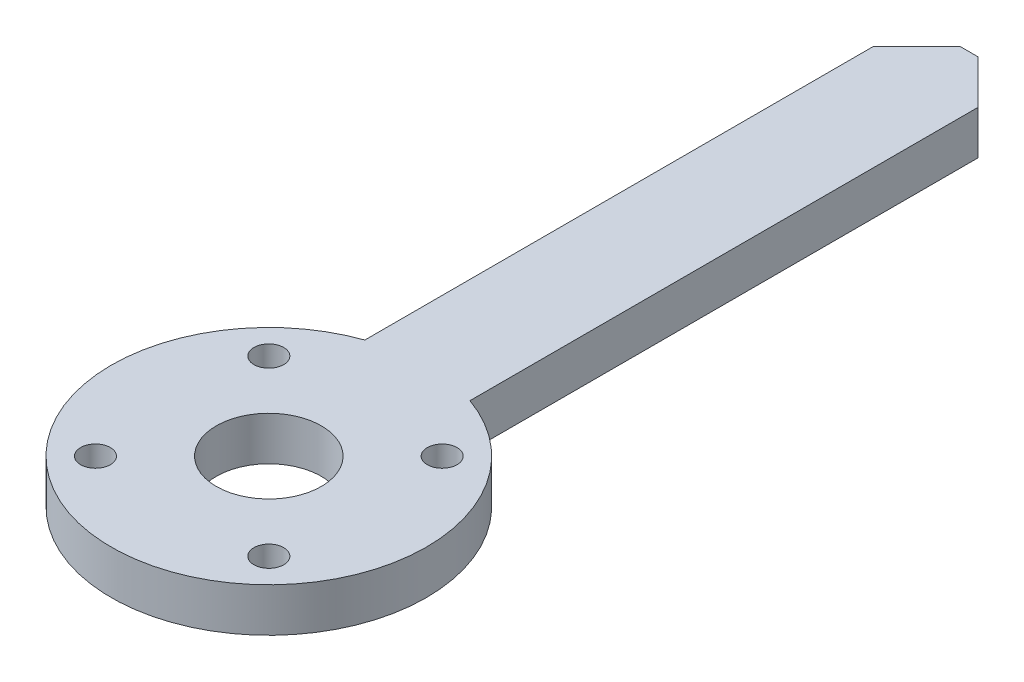
SolidWorks part; units mm, degrees
ref_plane "Front Plane" through (0, 0, 0) normal (0, 0, 1) x (1, 0, 0)
ref_plane "Top Plane" through (0, 0, 0) normal (0, 1, 0) x (1, 0, 0)
ref_plane "Right Plane" through (0, 0, 0) normal (1, 0, 0) x (0, 0, -1)
sketch "Sketch1" plane through (0, 0, 0) normal (0, 1, 0) x (1, 0, 0)
  circle A0 centre (0, 0) radius 18
  dimension "D1" = 36
extrude "Boss-Extrude2" add sketch "Sketch1" along normal blind 5
sketch "Sketch2" plane through (0, 0, 0) normal (0, 1, 0) x (1, 0, 0)
  line L0 (-2.75, 0) -> (2.75, 0) construction
  line L1 (-6, 0) -> (6, 0)
  line L2 (-6, 0) -> (-6, 80)
  line L3 (-6, 80) -> (6, 80)
  line L4 (6, 0) -> (6, 80)
  line L5 (0, 80) -> (0, 0) construction
  line L7 (-6, 40) -> (6, 40) construction
  line L8 (0, -2.75) -> (0, 2.75) construction
  point P12 (0, 40)
  dimension "D1" = 12
  dimension "D2" = 80
extrude "Boss-Extrude3" add sketch "Sketch2" along normal blind 5
sketch "Sketch3" plane through (0, 0, 0) normal (0, 1, 0) x (1, 0, 0)
  line L0 (0, 0) -> (9.8995, 9.8995) construction
  line L1 (-2.75, 0) -> (2.75, 0) construction
  circle A0 centre (9.8995, 9.8995) radius 1.7
  circle A1 centre (9.8995, -9.8995) radius 1.7
  circle A2 centre (-9.8995, -9.8995) radius 1.7
  circle A3 centre (-9.8995, 9.8995) radius 1.7
  circle A4 centre (0, 0) radius 6
  point P15 (0, 0)
  dimension "D3" = 3.4
  dimension "D5" = 12
  dimension "D1" = 45
  dimension "D2" = 14
  dimension "D4" = 4
extrude "Cut-Extrude1" cut sketch "Sketch3" along normal through all
chamfer "Chamfer1" distance 5 angle 45 2 edges at (-6, 2.5, -80) (6, 2.5, -80)
equation "\"pin_circle_R\" = 27"
equation "\"ecc\" = 1.5"
equation "\"n_pins\" = 11"
equation "\"pin_d\" = 3"
equation "\"out_pin_R\" = 18.5"
equation "\"disc_clr\" = 0.1"
equation "\"seat_6803\" = 26.1"
equation "\"seat_6806\" = 42.1"
equation "\"disc_t\" = 5"
equation "\"out_hole_clr\" = 0.5"
equation "\"boss_17\" = 17.13"
equation "\"rotor_bolt_R\" = 10"
equation "\"m25_clr\" = 2.8"
equation "\"m25_head\" = 5"
equation "\"insert_hole\" = 4.4"
equation "\"csk\" = 0.6"
equation "\"peg_d\" = 3.0"
equation "\"plug_d\" = 8.6"
equation "\"peg_clr\" = 0.3"
equation "\"m3_clr\" = 3.4"
equation "\"m3_head\" = 6.2"
equation "\"pin_press\" = 3.2"
equation "\"pin_slip\" = 3.35"
equation "\"hub_30\" = 30.18"
equation "\"hub_short\" = 0.2"
equation "\"m3_tap\" = 2.8"
equation "\"rear_plate_t\" = 2"
equation "\"motor_ring\" = 40.4"
equation "\"plug_shaft_d\" = 8.8"
equation "\"D3@Sketch3\"=\"m3_clr\""
